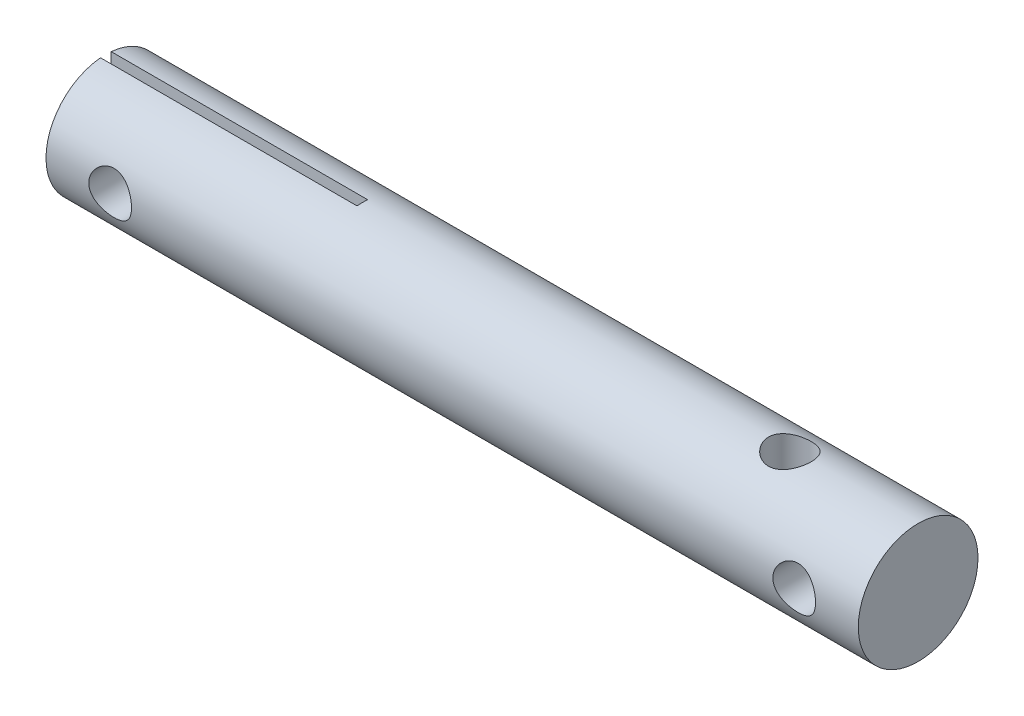
SolidWorks part; units mm, degrees
ref_plane "前视基准面" through (0, 0, 0) normal (0, 0, 1) x (1, 0, 0)
ref_plane "上视基准面" through (0, 0, 0) normal (0, 1, 0) x (1, 0, 0)
ref_plane "右视基准面" through (0, 0, 0) normal (1, 0, 0) x (0, 0, -1)
other "Configuration Table"
sketch "草图1" plane through (0, 0, 0) normal (1, 0, 0) x (0, 0, -1)
  circle A0 centre (0, 0) radius 2.8
  dimension "D1" = 5.6
extrude "凸台-拉伸1" add sketch "草图1" along normal blind 38
sketch "草图2" plane through (0, 0, 0) normal (-1, 0, 0) x (0, 0, 1)
  line L0 (0, 2.8) -> (0, -2.8) construction
  line L2 (-0.25, 3.1215) -> (0.25, 3.1215)
  line L3 (-0.25, 3.1215) -> (-0.25, -2.329)
  line L4 (-0.25, -2.329) -> (0.25, -2.329)
  line L5 (0.25, 3.1215) -> (0.25, -2.329)
  circle A0 centre (0, 0) radius 2.8 construction
  dimension "D1" = 0.5
  dimension "D2" = 0.25
extrude "切除-拉伸1" cut sketch "草图2" against normal blind 12
sketch "草图3" plane through (0, 0, 0.25) normal (0, 0, -1) x (-1, 0, 0)
  line L0 (0, -0.0056) -> (-6.0327, -0.0056) construction
  line L1 (0, -2.8) -> (0, 2.7888) construction
  line L2 (-38, 2.8) -> (-38, -2.8) construction
  circle A0 centre (-3, -0.0056) radius 1
  circle A1 centre (-35, -0.0056) radius 1
  dimension "D1" = 2
  dimension "D4" = 3
  dimension "D3" = 2
  dimension "D2" = 3
extrude "切除-拉伸2" cut sketch "草图3" against normal blind 10 and the other way blind 10
sketch "草图7" plane through (0, 0, 0) normal (0, 1, 0) x (1, 0, 0)
  line L0 (38, -2.8) -> (38, 2.8) construction
  circle A0 centre (32, 0) radius 1
  dimension "D2" = 2
  dimension "D1" = 6
extrude "切除-拉伸3" cut sketch "草图7" against normal blind 10 and the other way blind 10
